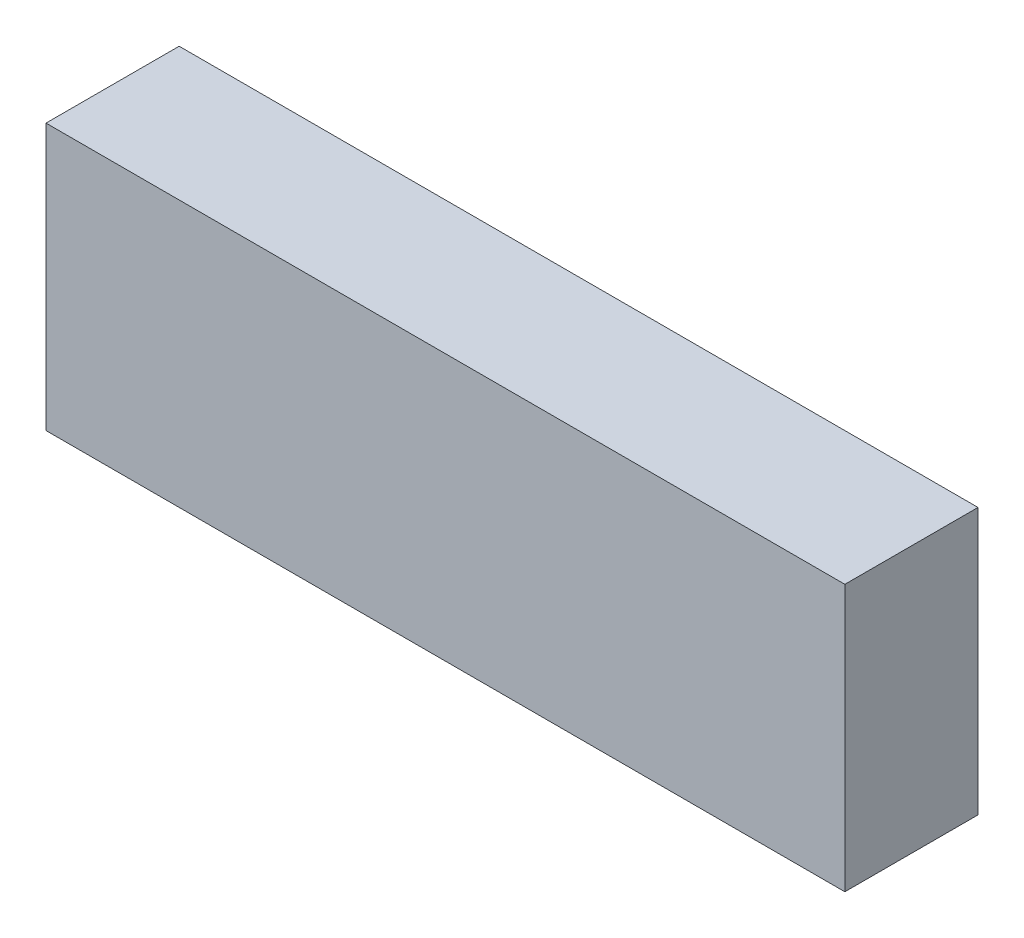
SolidWorks part; units mm, degrees
material "Maple"
ref_plane "Front Plane" through (0, 0, 0) normal (0, 0, 1) x (1, 0, 0)
ref_plane "Top Plane" through (0, 0, 0) normal (0, 1, 0) x (1, 0, 0)
ref_plane "Right Plane" through (0, 0, 0) normal (1, 0, 0) x (0, 0, -1)
sketch "Sketch1" plane through (0, 0, 0) normal (0, 1, 0) x (1, 0, 0)
  line L1 (15, 2.5) -> (-15, 2.5)
  line L2 (15, 2.5) -> (15, -2.5)
  line L3 (15, -2.5) -> (-15, -2.5)
  line L4 (-15, 2.5) -> (-15, -2.5)
  line L5 (15, 2.5) -> (-15, -2.5) construction
  line L6 (15, -2.5) -> (-15, 2.5) construction
  point P0 (0, 0)
  dimension "D1" = 30
  dimension "D2" = 5
extrude "Boss-Extrude1" add sketch "Sketch1" along normal blind 10
